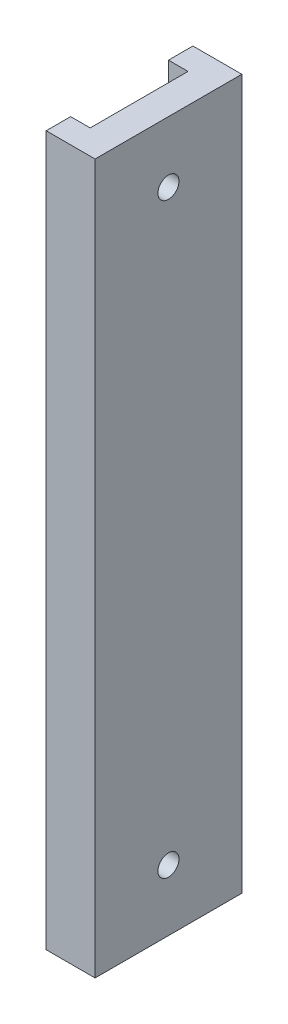
SolidWorks part; units mm, degrees
ref_plane "Front Plane" through (0, 0, 0) normal (0, 0, 1) x (1, 0, 0)
ref_plane "Top Plane" through (0, 0, 0) normal (0, 1, 0) x (1, 0, 0)
ref_plane "Right Plane" through (0, 0, 0) normal (1, 0, 0) x (0, 0, -1)
ref_plane "Plane1" through (0, 260, 0) normal (0, -1, 0) x (-1, 0, 0)
sketch "Sketch1" plane through (0, 260, 0) normal (0, -1, 0) x (-1, 0, 0)
  line L0 (71.5, -127.5) -> (61.5, -127.5)
  line L1 (61.5, -127.5) -> (61.5, -97.5)
  line L2 (61.5, -97.5) -> (71.5, -97.5)
  line L3 (71.5, -97.5) -> (71.5, -102.5)
  line L4 (71.5, -102.5) -> (67.5, -102.5)
  line L5 (67.5, -102.5) -> (67.5, -122.5)
  line L6 (67.5, -122.5) -> (71.5, -122.5)
  line L7 (71.5, -122.5) -> (71.5, -127.5)
  line L8 (68.9986, -122.5) -> (74.3631, -122.5) construction
  line L9 (68.9986, -102.5) -> (74.3631, -102.5) construction
  line L10 (67.5, -115.6369) -> (67.5, -121.0014) construction
  dimension "D1" = 5
  dimension "D2" = 10
  dimension "D3" = 6
extrude "Boss-Extrude1" add sketch "Sketch1" along normal blind 145
hole_wizard "M4 Clearance Hole1" positions "Sketch2" profile "Sketch4" hole size "M4" standard "ISO" end condition through all
sketch "Sketch2" plane through (-61.5, 0, 0) normal (1, 0, 0) x (0, 0, -1)
  line L0 (-112.5, 247.5) -> (-112.5, 127.5) construction
  line L2 (-97.5, 260) -> (-127.5, 260) construction
  line L4 (-112.5, 247.5) -> (-112.5, 260) construction
  line L7 (-112.5, 127.5) -> (-112.5, 115) construction
  line L8 (-97.5, 115) -> (-127.5, 115) construction
  point P1 (-112.5, 247.5)
  point P2 (-112.5, 127.5)
  point P7 (-112.5, 260)
  dimension "D1" = 120
sketch "Sketch4" plane through (-61.5, 247.5, 112.5) normal (0, 1, 0) x (0, 0, -1)
  line L0 (0, 0) -> (0, 10)
  line L1 (0, 10) -> (2.15, 10)
  line L2 (2.15, 10) -> (2.15, 0)
  line L5 (2.15, 0) -> (0, 0)
  line L11 (0, -6.35) -> (0, 107.95) construction
  dimension "Thru Hole Dia." = 4.3
  dimension "Thru Hole Depth" = 10
